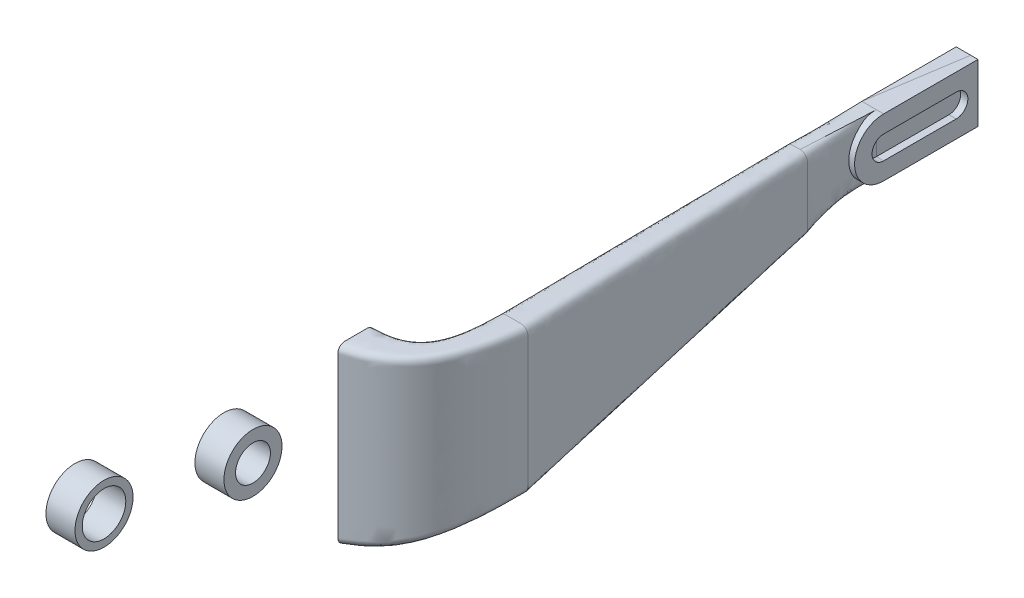
SolidWorks part; units mm, degrees
note: '?' marks a value the reader was unsure of. The reader was unsure of these and kept them because the rebuilt part matched: shared geometry of "Szkic3<4>", "Szkic4<3>", "Szkic7<4>".
ref_plane "Płaszczyzna przednia" through (0, 0, 0) normal (0, 0, 1) x (1, 0, 0)
ref_plane "Płaszczyzna górna" through (0, 0, 0) normal (0, 1, 0) x (1, 0, 0)
ref_plane "Płaszczyzna prawa" through (0, 0, 0) normal (1, 0, 0) x (0, 0, -1)
sketch "Baza - płaszczyzna górna" plane through (0, 0, 0) normal (0, 1, 0) x (1, 0, 0)
  line L0 (0, 0) -> (0, 512) construction
  line L1 (117.5, 147.6) -> (-117.5, 147.6) construction
  line L2 (135, 0) -> (-135, 0) construction
  line L3 (-117.5, 512) -> (117.5, 512) construction
  line L4 (-117.5, 512) -> (-117.5, 147.6) construction
  line L5 (117.5, 512) -> (117.5, 147.6) construction
  line L6 (117.5, 186) -> (-117.5, 186) construction
  line L7 (135, 22.5) -> (135, -22.5) construction
  line L8 (-135, 22.5) -> (-135, -22.5) construction
  line L9 (117.5, 512) -> (125, 512) construction
  line L10 (125, 512) -> (125, 147.6) construction
  line L11 (125, 147.6) -> (117.5, 147.6) construction
  point P2 (0, 487)
  point P7 (0, 0)
  point P10 (0, 512)
  point P12 (0, 147.6)
  point P16 (135, 0)
  dimension "D1" = 512
  dimension "D2" = 147.6
  dimension "D3" = 270
  dimension "D4" = 235
  dimension "D5" = 326
  dimension "D6" = 45
  dimension "D7" = 25
  dimension "D8" = 125
sketch "Baza - płaszczyzna prawa" plane through (0, 0, 0) normal (1, 0, 0) x (0, 0, -1)
  line L0 (0, 0) -> (512, 0) construction
  line L1 (0, 0) -> (512, 0) construction
  line L2 (147.6, 0) -> (147.6, -66) construction
  arc A2 (440.6668, 297.4126) -> (440.6668, -297.4126) centre (487, 0) ccw
  dimension "D5" = 301
  dimension "D1" = 66
  dimension "D2" = 147.6
ref_plane "Powierzchnia styku z ramą" through (135, 0, 0) normal (1, 0, 0) x (0, 0, -1)
sketch "Szkic - insert - rama" plane through (135, 0, 0) normal (1, 0, 0) x (0, 0, -1)
  circle A0 centre (0, 0) radius 20
  circle A1 centre (0, 0) radius 15
  dimension "D1" = 40
  dimension "D2" = 30
ref_plane "Powierzchnia graniczna koła" through (125, 0, 0) normal (1, 0, 0) x (0, 0, -1)
ref_plane "Płaszczyzna pracy łańcucha" through (100, 0, 0) normal (1, 0, 0) x (0, 0, -1)
sketch "Łańcuch - baza" plane through (100, 0, 0) normal (1, 0, 0) x (0, 0, -1)
  line L0 (0, 0) -> (-72.4444, -19.4114) construction
  line L1 (0, 0) -> (512, 0) construction
  dimension "D1" = 75
  dimension "D2" = 165
sketch "Łańcuch - zarys" plane through (100, 0, 0) normal (1, 0, 0) x (0, 0, -1)
  line L0 (-75.0521, 2.4335) -> (503.4658, 71.4924)
  line L1 (-83.5151, 37.5222) -> (483.2736, 147.733)
  line L2 (-72.4444, -19.4114) -> (512, 0) construction
  line L3 (-79.7129, -76.9542) -> (493.1396, -149.3135)
  line L4 (-73.5969, -41.3812) -> (508.2284, -71.9011)
  circle A0 centre (-72.4444, -19.4114) radius 22
  circle A1 centre (512, 0) radius 72
  arc A2 (-83.5151, 37.5222) -> (-79.7129, -76.9542) centre (-72.4444, -19.4114) ccw
  arc A3 (493.1396, -149.3135) -> (483.2736, 147.733) centre (512, 0) ccw
  point P0 (-72.4444, -19.4114)
  point P2 (512, 0)
  dimension "D1" = 44
  dimension "D2" = 144
  dimension "D3" = 116
  dimension "D4" = 301
ref_axis "Oś tynego koła" through (-117.5, 0, -512) along (1, 0, 0)?
ref_axis "Oś mocowania do ramy" through (135, 0, 0) along (-1, 0, 0)?
ref_axis "Oś mocowania linkage" through (0, -66, -147.6) along (1, 0, 0)?
sketch "Szkic - insert - linkage" plane through (0, 0, 0) normal (1, 0, 0) x (0, 0, -1)
  circle A0 centre (147.6, -66) radius 12
  circle A1 centre (147.6, -66) radius 20
  dimension "D1" = 40
  dimension "D2" = 24
extrude "Rama" add sketch "Szkic - insert - rama" against normal mid plane 20 from offset 55 offset against normal yes
extrude "Linkage" add sketch "Szkic - insert - linkage" along normal blind 20 from offset 25 separate body
sketch "Szkic - insert - tylne koło" plane through (125, 0, 0) normal (1, 0, 0) x (0, 0, -1)
  line L0 (487, 20) -> (552, 20)
  line L1 (512, 0) -> (147.6, 0) construction
  line L2 (487, -20) -> (552, -20)
  line L3 (537, 8) -> (487, 8)
  line L4 (537, -8) -> (487, -8)
  line L5 (552, -20) -> (552, 20)
  arc A1 (487, 8) -> (487, -8) centre (487, 0) ccw
  arc A2 (537, -8) -> (537, 8) centre (537, 0) ccw
  arc A3 (487, 20) -> (487, -20) centre (487, 0) ccw
  dimension "D1" = 40
  dimension "D3" = 8
  dimension "D2" = 65
  dimension "D4" = 487
  dimension "D5" = 537
extrude "Tylne koło" add sketch "Szkic - insert - tylne koło" along normal blind 15 separate body
sketch "Szkic otwór łańcuch" plane through (0, 0, 0) normal (0, 0, 1) x (1, 0, 0)
  line L3 (100, -130) -> (110, -130)
  line L13 (115, -125) -> (115, -45)
  line L14 (110, -40) -> (100, -40)
  line L15 (95, -45) -> (95, -125)
  arc A0 (100, -130) -> (95, -125) centre (100, -125) cw
  arc A1 (110, -130) -> (115, -125) centre (110, -125) ccw
  arc A2 (115, -45) -> (110, -40) centre (110, -45) ccw
  arc A3 (100, -40) -> (95, -45) centre (100, -45) ccw
  dimension "D1" = 5
  dimension "D2" = 95
  dimension "D3" = 20
  dimension "D4" = 40
  dimension "D5" = 90
ref_plane "Górna +30mm" through (0, 30, 0) normal (0, 1, 0) x (1, 0, 0)
ref_plane "Płaszczyzna1" through (0, 0, -552) normal (0, 0, 1) x (1, 0, 0)
sketch "Szkic2" plane through (0, 0, -552) normal (0, 0, 1) x (1, 0, 0)
  line L0 (125, -20) -> (135, -20)
  line L1 (125, -20) -> (125, 20) construction
  line L2 (125, -20) -> (125, 20)
  line L3 (135, -20) -> (135, 20)
  line L4 (135, 20) -> (125, 20)
  dimension "D1" = 10
ref_plane "Płaszczyzna2" through (0, 0, -487) normal (0, 0, 1) x (1, 0, 0)
sketch "Szkic3" plane through (0, 0, -487) normal (0, 0, 1) x (1, 0, 0)
  line L0 (125, -20) -> (125, 20) construction
  line L1 (125, -20) -> (125, 20)
  line L2 (125, 20) -> (135, 20)
  line L3 (135, 20) -> (135, -20)
  line L4 (135, -20) -> (125, -20)
  dimension "D1" = 10
ref_plane "Płaszczyzna3" through (0, 0, -437) normal (0, 0, 1) x (1, 0, 0)
sketch "Szkic4" plane through (0, 0, -437) normal (0, 0, 1) x (1, 0, 0)
  line L8 (125, 20) -> (135, 20) construction
  line L9 (135, 20) -> (135, -20) construction
  line L10 (125, -20) -> (125, 20) construction
  line L15 (135, -20) -> (125, -20) construction
  line L16 (135, -20) -> (125, -20) construction
  line L17 (125, -20) -> (125, 20) construction
  line L18 (135, 20) -> (135, -20) construction
  line L19 (125, 20) -> (135, 20) construction
  line L21 (127.5, 20) -> (132.5, 20)
  line L22 (122.5, 15) -> (122.5, -25)
  line L23 (127.5, -30) -> (132.5, -30)
  line L24 (137.5, 15) -> (137.5, -25)
  arc A0 (127.5, 20) -> (122.5, 15) centre (127.5, 15) ccw
  arc A1 (132.5, 20) -> (137.5, 15) centre (132.5, 15) cw
  arc A2 (132.5, -30) -> (137.5, -25) centre (132.5, -25) ccw
  arc A3 (122.5, -25) -> (127.5, -30) centre (127.5, -25) ccw
  point P0 (0, 0)
  point P11 (122.5, 20)
  point P14 (137.5, 20)
  point P19 (122.5, -30)
  point P22 (0, 0)
  dimension "D3" = 2.5
  dimension "D4" = 5
  dimension "D1" = 15
  dimension "D2" = 50
ref_plane "Płaszczyzna4" through (135, 0, 0) normal (1, 0, 0) x (0, 0, -1)
sketch "Szkic5" plane through (135, 0, 0) normal (1, 0, 0) x (0, 0, -1)
  line L0 (506.9623, -20) -> (467.0377, -20) construction
  line L1 (487, 20) -> (437, 20)
  spline S0 degree 3 poles (437, -30) (452.798, -22.2655) (470.3647, -20) (487, -20) knots 0 0 0 0 1 1 1 1
  point P0 (437, -30)
  point P2 (487, -20)
surface "Powierzchnia-Wyciągnięcie po profilach1"
surface "Powierzchnia-Wyciągnięcie po profilach2"
sketch "Szkic3<4>" plane through (0, 0, -487) normal (0, 0, 1) x (1, 0, 0) same geometry as "Szkic3"
ref_plane "Płaszczyzna5" through (0, 0, -237) normal (0, 0, 1) x (1, 0, 0)
sketch "Szkic7" plane through (0, 0, -237) normal (0, 0, 1) x (1, 0, 0)
  line L0 (127.5, 20) -> (132.5, 20) construction
  line L1 (127.5, 20) -> (132.5, 20) construction
  line L3 (130, 20) -> (140, 20)
  line L4 (125, 15) -> (125, -75)
  line L5 (130, -80) -> (140, -80)
  line L6 (145, 15) -> (145, -75)
  arc A0 (140, -80) -> (145, -75) centre (140, -75) ccw
  arc A1 (125, -75) -> (130, -80) centre (130, -75) ccw
  arc A2 (140, 20) -> (145, 15) centre (140, 15) cw
  arc A3 (130, 20) -> (125, 15) centre (130, 15) ccw
  point P8 (145, -80)
  point P13 (145, 20)
  point P16 (125, 20)
  dimension "D3" = 5
  dimension "D1" = 100
  dimension "D2" = 20
  dimension "D4" = 2.5
  dimension "D5" = 0
surface "Powierzchnia-Wyciągnięcie po profilach3"
sketch "Szkic4<3>" plane through (0, 0, -437) normal (0, 0, 1) x (1, 0, 0) same geometry as "Szkic4"
ref_plane "Płaszczyzna6" through (90, 0, 0) normal (1, 0, 0) x (0, 0, -1)
sketch "Szkic8" plane through (90, 0, 0) normal (1, 0, 0) x (0, 0, -1)
  line L0 (60.185, 20) -> (206.8274, 20) construction
  line L1 (186, 0) -> (186, 98.6419) construction
  line L3 (181, 20) -> (166, 20)
  line L4 (186, 15) -> (186, -95)
  line L5 (181, -100) -> (166, -100)
  line L6 (161, 15) -> (161, -95)
  arc A0 (186, -95) -> (181, -100) centre (181, -95) cw
  arc A1 (166, -100) -> (161, -95) centre (166, -95) cw
  arc A2 (181, 20) -> (186, 15) centre (181, 15) cw
  arc A3 (166, 20) -> (161, 15) centre (166, 15) ccw
  point P2 (186, 0)
  point P15 (161, -100)
  point P18 (186, 20)
  point P21 (161, 20)
  dimension "D4" = 5
  dimension "D1" = 20
  dimension "D2" = 120
  dimension "D3" = 25
sketch "Szkic9" plane through (0, 0, 0) normal (0, 1, 0) x (1, 0, 0)
  line L0 (125, 260.2457) -> (125, 213.7543) construction
  line L1 (111.3221, 186) -> (68.6779, 186) construction
  spline S0 degree 3 poles (90, 186) (116.6526, 186) (125, 196.0772) (125, 237) knots 0 0 0 0 1 1 1 1
  point P0 (125, 237)
  point P2 (90, 186)
surface "Powierzchnia-Wyciągnięcie po profilach5"
sketch "Szkic7<4>" plane through (0, 0, -237) normal (0, 0, 1) x (1, 0, 0) same geometry as "Szkic7"
